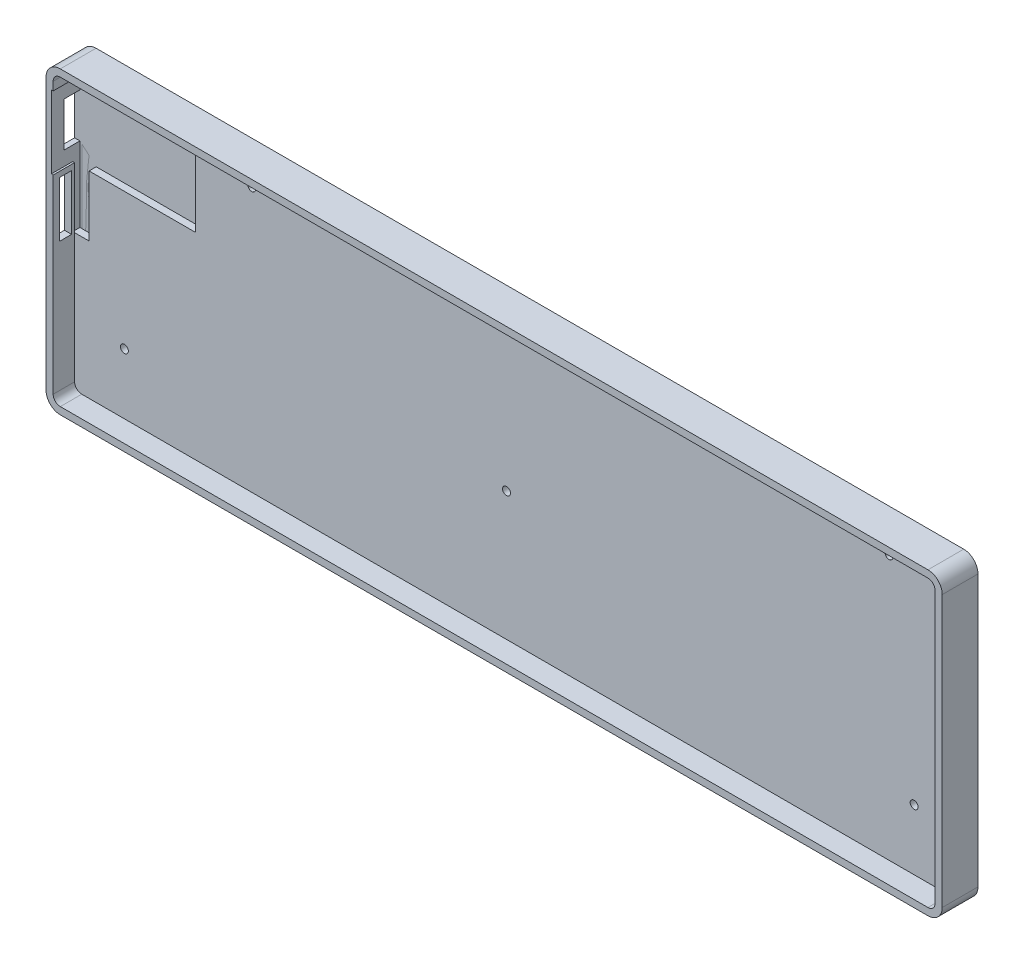
SolidWorks part; units mm, degrees
ref_plane "Front Plane" through (0, 0, 0) normal (0, 0, 1) x (1, 0, 0)
ref_plane "Top Plane" through (0, 0, 0) normal (0, 1, 0) x (1, 0, 0)
ref_plane "Right Plane" through (0, 0, 0) normal (1, 0, 0) x (0, 0, -1)
ref_plane "Plane1" through (0, 0, 1.6) normal (0, 0, 1) x (1, 0, 0)
sketch "Sketch1" plane through (0, 0, 1.6) normal (0, 0, 1) x (1, 0, 0)
  line L0 (342.62, -108.45) -> (99.95, -108.45)
  line L1 (97.95, -110.45) -> (97.95, -186.25)
  line L2 (99.95, -188.25) -> (342.62, -188.25)
  line L3 (344.62, -186.25) -> (344.62, -110.45)
  circle A0 centre (325.72, -114.3) radius 1.1
  circle A1 centre (330.8, -120) radius 0.95
  circle A2 centre (325.72, -120) radius 2.05
  circle A3 centre (320.64, -120) radius 0.95
  circle A4 centre (304.58, -120) radius 0.95
  circle A5 centre (299.5, -120) radius 2.05
  circle A6 centre (294.42, -120) radius 0.95
  circle A7 centre (285.58, -120) radius 0.95
  circle A8 centre (280.5, -120) radius 2.05
  circle A9 centre (329.53, -122.54) radius 1.5
  circle A10 centre (323.18, -125.08) radius 1.5
  circle A11 centre (327.37, -129) radius 0.15
  circle A12 centre (324.07, -129) radius 0.15
  circle A13 centre (303.31, -122.54) radius 1.5
  circle A14 centre (296.96, -125.08) radius 1.5
  circle A15 centre (284.31, -122.54) radius 1.5
  circle A16 centre (301.15, -129) radius 0.15
  circle A17 centre (297.85, -129) radius 0.15
  circle A18 centre (282.15, -129) radius 0.15
  circle A19 centre (275.42, -120) radius 0.95
  circle A20 centre (266.58, -120) radius 0.95
  circle A21 centre (261.5, -120) radius 2.05
  circle A22 centre (256.42, -120) radius 0.95
  circle A23 centre (247.58, -120) radius 0.95
  circle A24 centre (242.5, -120) radius 2.05
  circle A25 centre (237.42, -120) radius 0.95
  circle A26 centre (228.58, -120) radius 0.95
  circle A27 centre (223.5, -120) radius 2.05
  circle A28 centre (265.31, -122.54) radius 1.5
  circle A29 centre (277.96, -125.08) radius 1.5
  circle A30 centre (258.96, -125.08) radius 1.5
  circle A31 centre (278.85, -129) radius 0.15
  circle A32 centre (263.15, -129) radius 0.15
  circle A33 centre (259.85, -129) radius 0.15
  circle A34 centre (246.31, -122.54) radius 1.5
  circle A35 centre (239.96, -125.08) radius 1.5
  circle A36 centre (227.31, -122.54) radius 1.5
  circle A37 centre (220.96, -125.08) radius 1.5
  circle A38 centre (244.15, -129) radius 0.15
  circle A39 centre (240.85, -129) radius 0.15
  circle A40 centre (225.15, -129) radius 0.15
  circle A41 centre (221.85, -129) radius 0.15
  circle A42 centre (333.08, -139) radius 0.95
  circle A43 centre (328, -139) radius 2.05
  circle A44 centre (322.92, -139) radius 0.95
  circle A45 centre (309.33, -139) radius 0.95
  circle A46 centre (304.25, -139) radius 2.05
  circle A47 centre (299.17, -139) radius 0.95
  circle A48 centre (290.33, -139) radius 0.95
  circle A49 centre (285.25, -139) radius 2.05
  circle A50 centre (280.17, -139) radius 0.95
  circle A51 centre (331.81, -141.54) radius 1.5
  circle A52 centre (325.46, -144.08) radius 1.5
  circle A53 centre (329.65, -148) radius 0.15
  circle A54 centre (326.35, -148) radius 0.15
  circle A55 centre (308.06, -141.54) radius 1.5
  circle A56 centre (301.71, -144.08) radius 1.5
  circle A57 centre (289.06, -141.54) radius 1.5
  circle A58 centre (282.71, -144.08) radius 1.5
  circle A59 centre (305.9, -148) radius 0.15
  circle A60 centre (302.6, -148) radius 0.15
  circle A61 centre (286.9, -148) radius 0.15
  circle A62 centre (283.6, -148) radius 0.15
  circle A63 centre (271.33, -139) radius 0.95
  circle A64 centre (266.25, -139) radius 2.05
  circle A65 centre (261.17, -139) radius 0.95
  circle A66 centre (252.33, -139) radius 0.95
  circle A67 centre (247.25, -139) radius 2.05
  circle A68 centre (242.17, -139) radius 0.95
  circle A69 centre (233.33, -139) radius 0.95
  circle A70 centre (228.25, -139) radius 2.05
  circle A71 centre (223.17, -139) radius 0.95
  circle A72 centre (270.06, -141.54) radius 1.5
  circle A73 centre (251.06, -141.54) radius 1.5
  circle A74 centre (263.71, -144.08) radius 1.5
  circle A75 centre (267.9, -148) radius 0.15
  circle A76 centre (264.6, -148) radius 0.15
  circle A77 centre (244.71, -144.08) radius 1.5
  circle A78 centre (232.06, -141.54) radius 1.5
  circle A79 centre (225.71, -144.08) radius 1.5
  circle A80 centre (248.9, -148) radius 0.15
  circle A81 centre (245.6, -148) radius 0.15
  circle A82 centre (229.9, -148) radius 0.15
  circle A83 centre (226.6, -148) radius 0.15
  circle A84 centre (218.42, -120) radius 0.95
  circle A85 centre (209.58, -120) radius 0.95
  circle A86 centre (204.5, -120) radius 2.05
  circle A87 centre (199.42, -120) radius 0.95
  circle A88 centre (190.58, -120) radius 0.95
  circle A89 centre (185.5, -120) radius 2.05
  circle A90 centre (180.42, -120) radius 0.95
  circle A91 centre (171.58, -120) radius 0.95
  circle A92 centre (166.5, -120) radius 2.05
  circle A93 centre (161.42, -120) radius 0.95
  circle A94 centre (208.31, -122.54) radius 1.5
  circle A95 centre (189.31, -122.54) radius 1.5
  circle A96 centre (201.96, -125.08) radius 1.5
  circle A97 centre (206.15, -129) radius 0.15
  circle A98 centre (202.85, -129) radius 0.15
  circle A99 centre (182.96, -125.08) radius 1.5
  circle A100 centre (170.31, -122.54) radius 1.5
  circle A101 centre (163.96, -125.08) radius 1.5
  circle A102 centre (187.15, -129) radius 0.15
  circle A103 centre (183.85, -129) radius 0.15
  circle A104 centre (168.15, -129) radius 0.15
  circle A105 centre (164.85, -129) radius 0.15
  circle A106 centre (147.5, -114.3) radius 1.1
  circle A107 centre (129.49, -115.23) radius 0.5
  circle A108 centre (152.58, -120) radius 0.95
  circle A109 centre (147.5, -120) radius 2.05
  circle A110 centre (142.42, -120) radius 0.95
  circle A111 centre (133.58, -120) radius 0.95
  circle A112 centre (126.95, -115.23) radius 0.5
  circle A113 centre (124.41, -115.23) radius 0.5
  circle A114 centre (121.87, -115.23) radius 0.5
  circle A115 centre (119.33, -115.23) radius 0.5
  circle A116 centre (116.79, -115.23) radius 0.5
  circle A117 centre (114.25, -115.23) radius 0.5
  circle A118 centre (111.71, -115.23) radius 0.5
  circle A119 centre (109.17, -115.23) radius 0.5
  circle A120 centre (106.63, -115.23) radius 0.5
  circle A121 centre (104.09, -115.23) radius 0.5
  circle A122 centre (101.55, -115.23) radius 0.5
  circle A123 centre (128.5, -120) radius 2.05
  circle A124 centre (123.42, -120) radius 0.95
  circle A125 centre (114.58, -120) radius 0.95
  circle A126 centre (120.05, -121.15) radius 0.15
  circle A127 centre (109.5, -120) radius 2.05
  circle A128 centre (104.42, -120) radius 0.95
  circle A129 centre (100.875, -120.825) radius 0.15
  circle A130 centre (151.31, -122.54) radius 1.5
  circle A131 centre (144.96, -125.08) radius 1.5
  circle A132 centre (132.31, -122.54) radius 1.5
  circle A133 centre (149.15, -129) radius 0.15
  circle A134 centre (145.85, -129) radius 0.15
  circle A135 centre (129.49, -130.47) radius 0.5
  circle A136 centre (120.05, -124.45) radius 0.15
  circle A137 centre (125.96, -125.08) radius 1.5
  circle A138 centre (113.31, -122.54) radius 1.5
  circle A139 centre (100.875, -124.125) radius 0.15
  circle A140 centre (106.96, -125.08) radius 1.5
  circle A141 centre (126.95, -130.47) radius 0.5
  circle A142 centre (124.41, -130.47) radius 0.5
  circle A143 centre (121.87, -130.47) radius 0.5
  circle A144 centre (119.33, -130.47) radius 0.5
  circle A145 centre (116.79, -130.47) radius 0.5
  circle A146 centre (114.25, -130.47) radius 0.5
  circle A147 centre (111.71, -130.47) radius 0.5
  circle A148 centre (109.17, -130.47) radius 0.5
  circle A149 centre (106.63, -130.47) radius 0.5
  circle A150 centre (104.09, -130.47) radius 0.5
  circle A151 centre (101.55, -130.47) radius 0.5
  circle A152 centre (214.33, -139) radius 0.95
  circle A153 centre (209.25, -139) radius 2.05
  circle A154 centre (204.17, -139) radius 0.95
  circle A155 centre (195.33, -139) radius 0.95
  circle A156 centre (190.25, -139) radius 2.05
  circle A157 centre (185.17, -139) radius 0.95
  circle A158 centre (176.33, -139) radius 0.95
  circle A159 centre (171.25, -139) radius 2.05
  circle A160 centre (166.17, -139) radius 0.95
  circle A161 centre (213.06, -141.54) radius 1.5
  circle A162 centre (206.71, -144.08) radius 1.5
  circle A163 centre (194.06, -141.54) radius 1.5
  circle A164 centre (210.9, -148) radius 0.15
  circle A165 centre (207.6, -148) radius 0.15
  circle A166 centre (191.9, -148) radius 0.15
  circle A167 centre (175.06, -141.54) radius 1.5
  circle A168 centre (187.71, -144.08) radius 1.5
  circle A169 centre (168.71, -144.08) radius 1.5
  circle A170 centre (188.6, -148) radius 0.15
  circle A171 centre (172.9, -148) radius 0.15
  circle A172 centre (169.6, -148) radius 0.15
  circle A173 centre (157.33, -139) radius 0.95
  circle A174 centre (152.25, -139) radius 2.05
  circle A175 centre (147.17, -139) radius 0.95
  circle A176 centre (138.33, -139) radius 0.95
  circle A177 centre (133.25, -139) radius 2.05
  circle A178 centre (128.17, -139) radius 0.95
  circle A179 centre (116.955, -139) radius 0.95
  circle A180 centre (99.78, -137.775) radius 0.45
  circle A181 centre (111.875, -139) radius 2.05
  circle A182 centre (106.795, -139) radius 0.95
  circle A183 centre (99.78, -140.775) radius 0.45
  circle A184 centre (156.06, -141.54) radius 1.5
  circle A185 centre (149.71, -144.08) radius 1.5
  circle A186 centre (137.06, -141.54) radius 1.5
  circle A187 centre (130.71, -144.08) radius 1.5
  circle A188 centre (153.9, -148) radius 0.15
  circle A189 centre (150.6, -148) radius 0.15
  circle A190 centre (134.9, -148) radius 0.15
  circle A191 centre (131.6, -148) radius 0.15
  circle A192 centre (115.685, -141.54) radius 1.5
  circle A193 centre (109.335, -144.08) radius 1.5
  circle A194 centre (113.525, -148) radius 0.15
  circle A195 centre (110.225, -148) radius 0.15
  circle A196 centre (337.83, -158) radius 0.95
  circle A197 centre (332.75, -158) radius 2.05
  circle A198 centre (327.67, -158) radius 0.95
  circle A199 centre (318.83, -158) radius 0.95
  circle A200 centre (313.75, -158) radius 2.05
  circle A201 centre (308.67, -158) radius 0.95
  circle A202 centre (299.83, -158) radius 0.95
  circle A203 centre (294.75, -158) radius 2.05
  circle A204 centre (289.67, -158) radius 0.95
  circle A205 centre (280.83, -158) radius 0.95
  circle A206 centre (336.56, -160.54) radius 1.5
  circle A207 centre (330.21, -163.08) radius 1.5
  circle A208 centre (317.56, -160.54) radius 1.5
  circle A209 centre (311.21, -163.08) radius 1.5
  circle A210 centre (334.4, -167) radius 0.15
  circle A211 centre (331.1, -167) radius 0.15
  circle A212 centre (315.4, -167) radius 0.15
  circle A213 centre (312.1, -167) radius 0.15
  circle A214 centre (298.56, -160.54) radius 1.5
  circle A215 centre (279.56, -160.54) radius 1.5
  circle A216 centre (292.21, -163.08) radius 1.5
  circle A217 centre (296.4, -167) radius 0.15
  circle A218 centre (293.1, -167) radius 0.15
  circle A219 centre (275.75, -158) radius 2.05
  circle A220 centre (270.67, -158) radius 0.95
  circle A221 centre (261.83, -158) radius 0.95
  circle A222 centre (256.75, -158) radius 2.05
  circle A223 centre (251.67, -158) radius 0.95
  circle A224 centre (242.83, -158) radius 0.95
  circle A225 centre (237.75, -158) radius 2.05
  circle A226 centre (232.67, -158) radius 0.95
  circle A227 centre (223.83, -158) radius 0.95
  circle A228 centre (273.21, -163.08) radius 1.5
  circle A229 centre (260.56, -160.54) radius 1.5
  circle A230 centre (254.21, -163.08) radius 1.5
  circle A231 centre (277.4, -167) radius 0.15
  circle A232 centre (274.1, -167) radius 0.15
  circle A233 centre (258.4, -167) radius 0.15
  circle A234 centre (255.1, -167) radius 0.15
  circle A235 centre (241.56, -160.54) radius 1.5
  circle A236 centre (235.21, -163.08) radius 1.5
  circle A237 centre (222.56, -160.54) radius 1.5
  circle A238 centre (239.4, -167) radius 0.15
  circle A239 centre (236.1, -167) radius 0.15
  circle A240 centre (220.4, -167) radius 0.15
  circle A241 centre (332.75, -171.3) radius 1.1
  circle A242 centre (337.83, -177) radius 0.95
  circle A243 centre (332.75, -177) radius 2.05
  circle A244 centre (327.67, -177) radius 0.95
  circle A245 centre (318.83, -177) radius 0.95
  circle A246 centre (313.75, -177) radius 2.05
  circle A247 centre (308.67, -177) radius 0.95
  circle A248 centre (299.83, -177) radius 0.95
  circle A249 centre (294.75, -177) radius 2.05
  circle A250 centre (289.67, -177) radius 0.95
  circle A251 centre (280.83, -177) radius 0.95
  circle A252 centre (336.56, -179.54) radius 1.5
  circle A253 centre (330.21, -182.08) radius 1.5
  circle A254 centre (317.56, -179.54) radius 1.5
  circle A255 centre (311.21, -182.08) radius 1.5
  circle A256 centre (334.4, -186) radius 0.15
  circle A257 centre (331.1, -186) radius 0.15
  circle A258 centre (315.4, -186) radius 0.15
  circle A259 centre (312.1, -186) radius 0.15
  circle A260 centre (298.56, -179.54) radius 1.5
  circle A261 centre (279.56, -179.54) radius 1.5
  circle A262 centre (292.21, -182.08) radius 1.5
  circle A263 centre (296.4, -186) radius 0.15
  circle A264 centre (293.1, -186) radius 0.15
  circle A265 centre (256.813, -170.015) radius 1.524
  circle A266 centre (275.75, -177) radius 2.05
  circle A267 centre (270.67, -177) radius 0.95
  circle A268 centre (249.955, -177) radius 0.95
  circle A269 centre (232.937, -170.015) radius 1.524
  circle A270 centre (244.875, -177) radius 2.05
  circle A271 centre (239.795, -177) radius 0.95
  circle A272 centre (273.21, -182.08) radius 1.5
  circle A273 centre (277.4, -186) radius 0.15
  circle A274 centre (274.1, -186) radius 0.15
  circle A275 centre (256.813, -185.225) radius 1.9939
  circle A276 centre (248.685, -179.54) radius 1.5
  circle A277 centre (242.335, -182.08) radius 1.5
  circle A278 centre (246.525, -186) radius 0.15
  circle A279 centre (243.225, -186) radius 0.15
  circle A280 centre (232.937, -185.225) radius 1.9939
  circle A281 centre (218.75, -152.3) radius 1.1
  circle A282 centre (218.75, -158) radius 2.05
  circle A283 centre (213.67, -158) radius 0.95
  circle A284 centre (204.83, -158) radius 0.95
  circle A285 centre (199.75, -158) radius 2.05
  circle A286 centre (194.67, -158) radius 0.95
  circle A287 centre (185.83, -158) radius 0.95
  circle A288 centre (180.75, -158) radius 2.05
  circle A289 centre (175.67, -158) radius 0.95
  circle A290 centre (166.83, -158) radius 0.95
  circle A291 centre (161.75, -158) radius 2.05
  circle A292 centre (216.21, -163.08) radius 1.5
  circle A293 centre (203.56, -160.54) radius 1.5
  circle A294 centre (197.21, -163.08) radius 1.5
  circle A295 centre (217.1, -167) radius 0.15
  circle A296 centre (201.4, -167) radius 0.15
  circle A297 centre (198.1, -167) radius 0.15
  circle A298 centre (184.56, -160.54) radius 1.5
  circle A299 centre (178.21, -163.08) radius 1.5
  circle A300 centre (165.56, -160.54) radius 1.5
  circle A301 centre (159.21, -163.08) radius 1.5
  circle A302 centre (182.4, -167) radius 0.15
  circle A303 centre (179.1, -167) radius 0.15
  circle A304 centre (163.4, -167) radius 0.15
  circle A305 centre (160.1, -167) radius 0.15
  circle A306 centre (130.6, -154.325) radius 0.375
  circle A307 centre (156.67, -158) radius 0.95
  circle A308 centre (147.83, -158) radius 0.95
  circle A309 centre (142.75, -158) radius 2.05
  circle A310 centre (137.67, -158) radius 0.95
  circle A311 centre (128.6, -154.325) radius 0.375
  circle A312 centre (121.705, -158) radius 0.95
  circle A313 centre (116.625, -158) radius 2.05
  circle A314 centre (111.545, -158) radius 0.95
  circle A315 centre (146.56, -160.54) radius 1.5
  circle A316 centre (140.21, -163.08) radius 1.5
  circle A317 centre (144.4, -167) radius 0.15
  circle A318 centre (141.1, -167) radius 0.15
  circle A319 centre (120.435, -160.54) radius 1.5
  circle A320 centre (114.085, -163.08) radius 1.5
  circle A321 centre (118.275, -167) radius 0.15
  circle A322 centre (114.975, -167) radius 0.15
  circle A323 centre (209.313, -170.04) radius 1.524
  circle A324 centre (202.455, -177) radius 0.95
  circle A325 centre (197.375, -177) radius 2.05
  circle A326 centre (192.295, -177) radius 0.95
  circle A327 centre (185.437, -170.04) radius 1.524
  circle A328 centre (164.455, -177) radius 0.95
  circle A329 centre (159.375, -177) radius 2.05
  circle A330 centre (201.185, -179.54) radius 1.5
  circle A331 centre (194.835, -182.08) radius 1.5
  circle A332 centre (209.313, -185.25) radius 1.9939
  circle A333 centre (199.025, -186) radius 0.15
  circle A334 centre (195.725, -186) radius 0.15
  circle A335 centre (163.185, -179.54) radius 1.5
  circle A336 centre (185.437, -185.25) radius 1.9939
  circle A337 centre (161.025, -186) radius 0.15
  circle A338 centre (154.295, -177) radius 0.95
  circle A339 centre (140.705, -177) radius 0.95
  circle A340 centre (135.625, -177) radius 2.05
  circle A341 centre (130.545, -177) radius 0.95
  circle A342 centre (111.875, -171.3) radius 1.1
  circle A343 centre (116.955, -177) radius 0.95
  circle A344 centre (111.875, -177) radius 2.05
  circle A345 centre (106.795, -177) radius 0.95
  circle A346 centre (156.835, -182.08) radius 1.5
  circle A347 centre (139.435, -179.54) radius 1.5
  circle A348 centre (133.085, -182.08) radius 1.5
  circle A349 centre (157.725, -186) radius 0.15
  circle A350 centre (137.275, -186) radius 0.15
  circle A351 centre (133.975, -186) radius 0.15
  circle A352 centre (115.685, -179.54) radius 1.5
  circle A353 centre (109.335, -182.08) radius 1.5
  circle A354 centre (113.525, -186) radius 0.15
  circle A355 centre (110.225, -186) radius 0.15
  arc A356 (344.62, -110.45) -> (342.62, -108.45) centre (342.62, -110.45) ccw
  arc A357 (99.95, -108.45) -> (97.95, -110.45) centre (99.95, -110.45) ccw
  arc A358 (97.95, -186.25) -> (99.95, -188.25) centre (99.95, -186.25) ccw
  arc A359 (342.62, -188.25) -> (344.62, -186.25) centre (342.62, -186.25) ccw
extrude "Boss-Extrude1" add sketch "Sketch1" against normal blind 1.6
sketch "Sketch2" plane through (0, 0, 1.6) normal (0, 0, 1) x (1, 0, 0)
  line L0 (99.95, -108.45) -> (342.62, -108.45)
  line L1 (344.62, -110.45) -> (344.62, -186.25)
  line L2 (342.62, -188.25) -> (99.95, -188.25)
  line L3 (97.95, -186.25) -> (97.95, -110.45)
  line L4 (97.95, -110.45) -> (97.95, -186.25)
  line L5 (99.95, -106.45) -> (342.62, -106.45)
  line L6 (346.62, -110.45) -> (346.62, -186.25)
  line L7 (342.62, -190.25) -> (99.95, -190.25)
  line L8 (95.95, -110.45) -> (95.95, -186.25)
  circle A0 centre (147.5, -114.3) radius 1.1
  circle A1 centre (325.72, -114.3) radius 1.1
  circle A2 centre (332.75, -171.3) radius 1.1
  circle A3 centre (218.75, -152.3) radius 1.1138
  circle A4 centre (111.875, -171.3) radius 1.106
  arc A5 (342.62, -108.45) -> (344.62, -110.45) centre (342.62, -110.45) cw
  arc A6 (344.62, -186.25) -> (342.62, -188.25) centre (342.62, -186.25) cw
  arc A7 (99.95, -188.25) -> (97.95, -186.25) centre (99.95, -186.25) cw
  arc A8 (97.95, -110.45) -> (99.95, -108.45) centre (99.95, -110.45) cw
  arc A9 (95.95, -110.45) -> (99.95, -106.45) centre (99.95, -110.45) cw
  arc A10 (342.62, -106.45) -> (346.62, -110.45) centre (342.62, -110.45) cw
  arc A11 (346.62, -186.25) -> (342.62, -190.25) centre (342.62, -186.25) cw
  arc A12 (99.95, -190.25) -> (95.95, -186.25) centre (99.95, -186.25) cw
  dimension "D1" = 2
extrude "Boss-Extrude2" add sketch "Sketch2" along normal blind 8 and the other way blind 2 separate body contours A12 L7 A11 L6 A10 L5 A9 L8 L3 A8 L0 A5 L1 A6 L2 A7 region at (221.285, -106.7143, 1.6)
sketch "Sketch5" plane through (0, 0, 0) normal (0, 0, 1) x (1, 0, 0)
  line L0 (99.95, -108.45) -> (342.62, -108.45)
  line L1 (344.62, -110.45) -> (344.62, -186.25)
  line L2 (342.62, -188.25) -> (99.95, -188.25)
  line L3 (97.95, -186.25) -> (97.95, -110.45)
  line L4 (97.95, -110.45) -> (97.95, -186.25)
  line L5 (99.95, -106.45) -> (342.62, -106.45)
  line L6 (346.62, -110.45) -> (346.62, -186.25)
  line L7 (342.62, -190.25) -> (99.95, -190.25)
  line L8 (95.95, -110.45) -> (95.95, -186.25)
  circle A0 centre (147.5, -114.3) radius 1.1
  circle A1 centre (325.72, -114.3) radius 1.1
  circle A2 centre (332.75, -171.3) radius 1.1
  circle A3 centre (218.75, -152.3) radius 1.1138
  circle A4 centre (111.875, -171.3) radius 1.106
  arc A5 (342.62, -108.45) -> (344.62, -110.45) centre (342.62, -110.45) cw
  arc A6 (344.62, -186.25) -> (342.62, -188.25) centre (342.62, -186.25) cw
  arc A7 (99.95, -188.25) -> (97.95, -186.25) centre (99.95, -186.25) cw
  arc A8 (97.95, -110.45) -> (99.95, -108.45) centre (99.95, -110.45) cw
  arc A9 (95.95, -110.45) -> (99.95, -106.45) centre (99.95, -110.45) cw
  arc A10 (342.62, -106.45) -> (346.62, -110.45) centre (342.62, -110.45) cw
  arc A11 (346.62, -186.25) -> (342.62, -190.25) centre (342.62, -186.25) cw
  arc A12 (99.95, -190.25) -> (95.95, -186.25) centre (99.95, -186.25) cw
  dimension "D1" = 2
extrude "Boss-Extrude5" add sketch "Sketch5" along normal blind 2 and the other way blind 2 from offset 1.6 contours A8 L3 A7 L2 A6 L1 A5 L0 A4 A3 A2 A1 A0 region at (221.2794, -148.3535, 0)
sketch "Sketch6" plane through (0, 0, 3.6) normal (0, 0, 1) x (1, 0, 0)
  line L1 (131.7363, -112.7927) -> (99.2016, -112.7927)
  line L2 (131.7363, -112.7927) -> (131.7363, -133.1474)
  line L3 (131.7363, -133.1474) -> (99.2016, -133.1474)
  line L4 (99.2016, -112.7927) -> (99.2016, -133.1474)
extrude "Cut-Extrude1" cut sketch "Sketch6" against normal blind 2
sketch "Sketch7" plane through (99.2016, 0, 0) normal (1, 0, 0) x (0, 0, -1)
  line L0 (-1.6, 96.4207) -> (-1.6, -96.4207) construction
  line L1 (-1.6, -116.7927) -> (-6.1, -116.7927)
  line L2 (-1.6, -116.7927) -> (-1.6, -129.1474)
  line L3 (-1.6, -129.1474) -> (-6.1, -129.1474)
  line L4 (-6.1, -116.7927) -> (-6.1, -129.1474)
  line L5 (-1.6, -112.7927) -> (-1.6, -133.1474)
  line L6 (-1.6, -112.7927) -> (-3.6, -112.7927) construction
  line L7 (-1.6, -112.7927) -> (-1.6, -133.1474) construction
  line L8 (-1.6, -133.1474) -> (-3.6, -133.1474) construction
  line M5 (-3.6, -112.7927) -> (-3.6, -133.1474)
  line M7 (-1.6, -133.1474) -> (-1.6, -112.7927)
  dimension "D1" = 4
  dimension "D2" = 4
  dimension "D3" = 4.5
extrude "Cut-Extrude2" cut sketch "Sketch7" against normal through all contours L1 L4 L3 M5 | L3 L1 M7 M5 region at (99.2016, -122.9701, 2.6) region at (99.2016, -122.9701, 4.85)
sketch "Sketch8" plane through (0, 0, 3.6) normal (0, 0, 1) x (1, 0, 0)
  line L0 (99.2016, -112.7927) -> (97.4393, -112.7927)
  line L1 (97.4393, -112.7927) -> (97.4393, -133.1546)
  line L2 (97.4393, -133.1546) -> (99.2016, -133.1474)
  line L3 (99.2016, -133.1474) -> (99.2016, -112.7927)
extrude "Cut-Extrude3" cut sketch "Sketch8" against normal blind 2 and the other way blind 10
sketch "Sketch9" plane through (0, 0, 3.6) normal (0, 0, 1) x (1, 0, 0)
  line L0 (99.2016, -133.1474) -> (131.7363, -133.1474) construction
  line L1 (101.9996, -133.1474) -> (97.4393, -133.1474)
  line L2 (101.9996, -133.1474) -> (101.9996, -150.1208)
  line L3 (101.9996, -150.1208) -> (97.4393, -150.1208)
  line L4 (97.4393, -133.1474) -> (97.4393, -150.1208)
  point P6 (97.4393, -133.1546)
  point P7 (101.9996, -150.1208)
extrude "Cut-Extrude4" cut sketch "Sketch9" against normal blind 2
sketch "Sketch11" plane through (97.95, 0, 0) normal (1, 0, 0) x (0, 0, -1)
  line L1 (-7.8722, -150.1138) -> (-4.4425, -150.1138)
  line L2 (-7.8722, -150.1138) -> (-7.8722, -134.6554)
  line L3 (-7.8722, -134.6554) -> (-4.4425, -134.6554)
  line L4 (-4.4425, -150.1138) -> (-4.4425, -134.6554)
extrude "Cut-Extrude6" cut sketch "Sketch11" against normal blind 2
